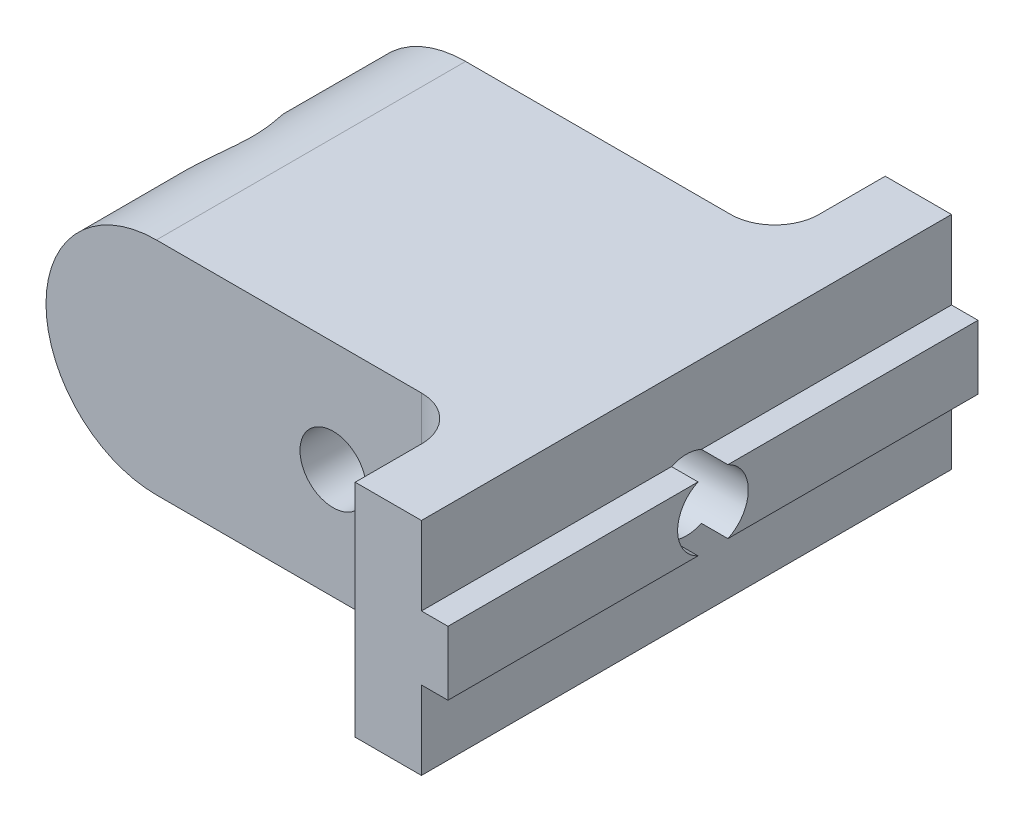
SolidWorks part; units mm, degrees
ref_plane "Front Plane" through (0, 0, 0) normal (0, 0, 1) x (1, 0, 0)
ref_plane "Top Plane" through (0, 0, 0) normal (0, 1, 0) x (1, 0, 0)
ref_plane "Right Plane" through (0, 0, 0) normal (1, 0, 0) x (0, 0, -1)
sketch "Esquisse1" plane through (0, 0, 0) normal (0, 0, 1) x (1, 0, 0)
  line L0 (-11, 5) -> (-11, -5)
  line L1 (-11, 5) -> (11, 5)
  line L2 (11, 5) -> (11, 1.45)
  line L3 (11, 1.45) -> (12.2, 1.45)
  line L4 (12.2, 1.45) -> (12.2, -1.45)
  line L5 (12.2, -1.45) -> (11, -1.45)
  line L6 (11, -1.45) -> (11, -5)
  line L7 (11, -5) -> (-11, -5)
  point P8 (12.2, 0)
  point P10 (0, -5)
  dimension "D1" = 2.9
  dimension "D2" = 10
  dimension "D3" = 1.2
  dimension "D4" = 22
extrude "Main Extrusion" add sketch "Esquisse1" along normal blind 24
sketch "Esquisse2" plane through (0, 5, 0) normal (0, 1, 0) x (1, 0, 0)
  line L0 (-11, -24) -> (-11, 0) construction
  line L1 (-11, 0) -> (8, 0)
  line L2 (-11, 0) -> (-11, -5)
  line L3 (-11, -5) -> (8, -5)
  line L4 (8, 0) -> (8, -5)
  line L5 (11, -24) -> (-11, -24) construction
  line L6 (-11, -24) -> (8, -24)
  line L7 (-11, -24) -> (-11, -19)
  line L8 (-11, -19) -> (8, -19)
  line L9 (8, -24) -> (8, -19)
  line L10 (11, 0) -> (-11, 0) construction
  line L12 (11, -24) -> (11, 0) construction
  point P12 (-15, 0)
  dimension "D1" = 3
  dimension "D2" = 5
extrude "External Hole" cut sketch "Esquisse2" against normal through all
sketch "Esquisse3" plane through (8, 0, 0) normal (-1, 0, 0) x (0, 0, 1)
  line L0 (24, -5) -> (19, -5) construction
  line L1 (24, -5) -> (24, 5) construction
  line L2 (5, -5) -> (0, -5) construction
  line L3 (19, -5) -> (5, -5) construction
  circle A1 centre (12, 0) radius 1.6
  point P6 (21.5, -5)
  point P7 (0, 0)
  point P10 (24, 0)
  point P11 (0, 0)
  point P12 (0, 0)
  point P15 (2.5, -5)
  point P16 (0, 0)
  point P17 (12.3908, 0)
  point P20 (12, -5)
  dimension "D1" = 3.2
extrude "MakerBeamFixingHole" cut sketch "Esquisse3" against normal through all
sketch "Esquisse4" plane through (0, 0, 19) normal (0, 0, 1) x (1, 0, 0)
  line L0 (8, -5) -> (8, 5) construction
  circle A0 centre (2, 0) radius 1.5
  point P4 (0, 0)
  dimension "D1" = 3
  dimension "D2" = 6
extrude "HoleLinkWithCodersSupport" cut sketch "Esquisse4" against normal through all
sketch "Esquisse5" plane through (-11, 0, 0) normal (-1, 0, 0) x (0, 0, 1)
  line L0 (19, 5) -> (5, 5) construction
  line L1 (5, -5) -> (5, 5) construction
  circle A0 centre (12, 0) radius 4.25
  point P2 (0, 0)
  point P5 (12, 5)
  point P8 (5, 0)
  dimension "D1" = 8.5
extrude "Enlèv. mat.-Extru.4" cut sketch "Esquisse5" against normal up to surface (19 mm away) up to face at (8, 0, 2.5)
fillet "Congé2" radius 2 2 edges at (8, 0, 19) (8, 0, 5)
fillet "Congé3" radius 5 2 edges at (-11, -5, 12) (-11, 5, 12)
